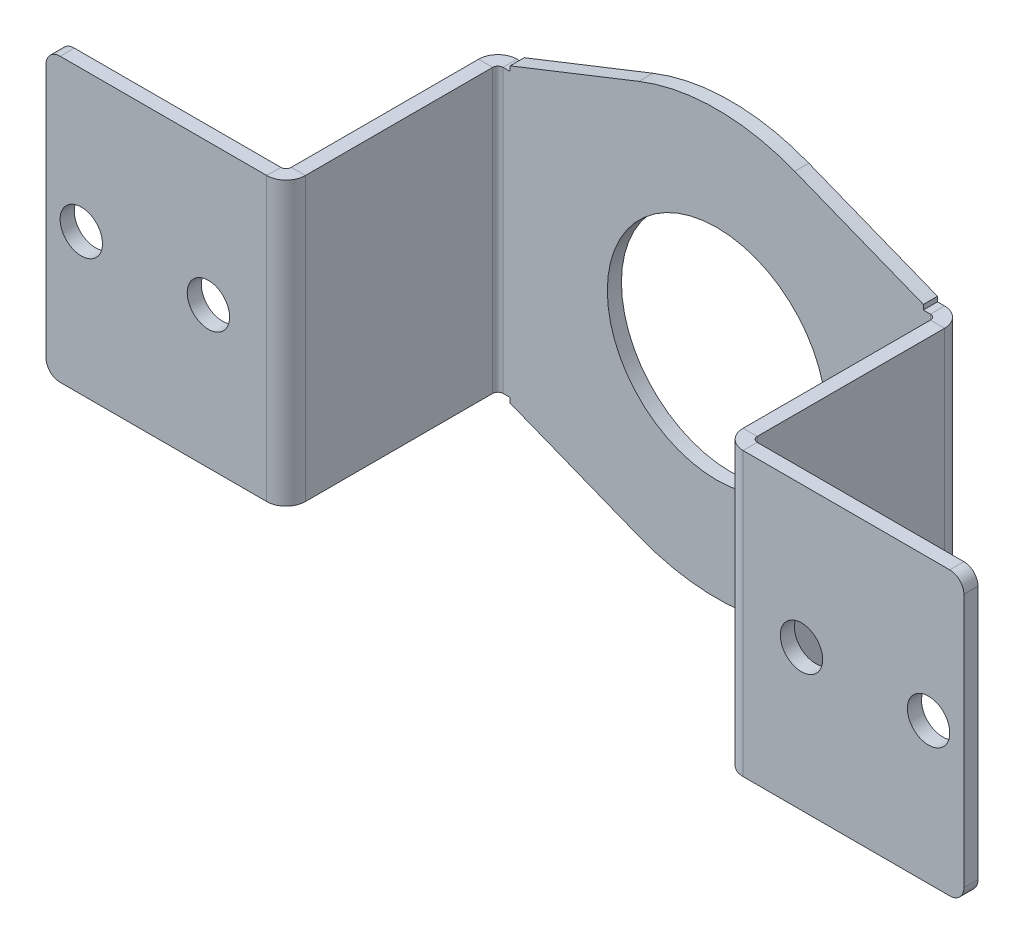
SolidWorks part; units mm, degrees
note: The reader was unsure of these and kept them because the rebuilt part matched: flange length of "Edge-Flange1", "Edge-Flange2".
material "1023 Carbon Steel Sheet (SS)"
ref_plane "Front Plane" through (0, 0, 0) normal (0, 0, 1) x (1, 0, 0)
ref_plane "Top Plane" through (0, 0, 0) normal (0, 1, 0) x (1, 0, 0)
ref_plane "Right Plane" through (0, 0, 0) normal (1, 0, 0) x (0, 0, -1)
sketch "Sketch1" plane through (0, 0, 0) normal (0, 0, 1) x (1, 0, 0)
  line L0 (0, 0) -> (-65, 0) construction
  line L2 (-31, 20) -> (-11.0341, 27.8971)
  line L3 (-31, -20) -> (-11.0341, -27.8971)
  line L4 (-31, 20) -> (-31, -20)
  line L5 (0, 0) -> (0, 30) construction
  line L6 (31, -20) -> (11.0341, -27.8971)
  line L7 (31, 20) -> (31, -20)
  line L8 (31, 20) -> (11.0341, 27.8971)
  circle A0 centre (0, 0) radius 15.5
  arc A1 (-11.0341, -27.8971) -> (11.0341, -27.8971) centre (0, 0) ccw
  arc A2 (11.0341, 27.8971) -> (-11.0341, 27.8971) centre (0, 0) ccw
  point P7 (-65, 0)
  point P13 (-31, 0)
  dimension "D1" = 31
  dimension "D2" = 60
  dimension "D3" = 40
  dimension "D5" = 31
base flange "Base-Flange1" sketch "Sketch1" thickness 2 reverse thickness direction no parameters "D1"=0.7366
edge flange "Edge-Flange1" sketch "Sketch8" flange profiles "Sketch8", "Sketch10" flange angle 90 flange length 30 flange position material outside bend radius 0.7366 thickness 2 relief rectangular parameters "D6"=10, "D8"=1
sketch "Sketch8" plane through (-31, 0, 0) normal (-1, 0, 0) x (0, -1, 0)
  line L2 (-20, 0) -> (-20, 28)
  line L3 (-20, 28) -> (20, 28)
  line L4 (20, 28) -> (20, 0)
  line L7 (-20, 0) -> (20, 0) construction
  line L8 (-20, 0) -> (20, 0)
sketch "Sketch10" plane through (31, 0, 0) normal (1, 0, 0) x (0, 1, 0)
  line L0 (-20, 0) -> (20, 0) construction
  line L1 (-20, 0) -> (20, 0)
  line L2 (-20, 0) -> (-20, 28)
  line L3 (-20, 28) -> (20, 28)
  line L4 (20, 28) -> (20, 0)
bend "EdgeBend1" bend radius 0.7366 bend angle 90 parameters "D5"=1
bend "EdgeBend2" bend radius 0.7366 bend angle 90 parameters "D5"=3
edge flange "Edge-Flange2" sketch "Sketch15" flange profiles "Sketch15", "Sketch16" flange angle 90 flange length 34 flange position material outside bend radius 0.7366 thickness 2 relief rectangular parameters "D6"=10, "D8"=1
sketch "Sketch15" plane through (-33, 0, 28) normal (0, 0, 1) x (0, 1, 0)
  line L2 (-20, 0) -> (-20, 32)
  line L3 (-20, 32) -> (20, 32)
  line L4 (20, 32) -> (20, 0)
  line L7 (-20, 0) -> (20, 0) construction
  line L8 (-20, 0) -> (20, 0)
sketch "Sketch16" plane through (33, 0, 28) normal (0, 0, 1) x (0, -1, 0)
  line L0 (-20, 0) -> (20, 0) construction
  line L1 (-20, 0) -> (20, 0)
  line L2 (-20, 0) -> (-20, 32)
  line L3 (-20, 32) -> (20, 32)
  line L4 (20, 32) -> (20, 0)
bend "EdgeBend3" bend radius 0.7366 bend angle 90 parameters "D5"=4
bend "EdgeBend4" bend radius 0.7366 bend angle 90 parameters "D5"=5
sketch "Sketch17" plane through (0, 0, 28) normal (0, 0, -1) x (-1, 0, 0)
  circle A1 centre (60, 0) radius 3
  circle A2 centre (42, 0) radius 3
  circle A3 centre (-60, 0) radius 3
  circle A4 centre (-42, 0) radius 3
  dimension "D1" = 6
  dimension "D2" = 6
  dimension "D3" = 42
  dimension "D4" = 60
  dimension "D5" = 42
  dimension "D6" = 60
extrude "Cut-Extrude1" cut sketch "Sketch17" against normal blind 10 normal cut yes
fillet "Fillet1" radius 2 4 edges at (-65, -20, 29) (65, 20, 29) (65, -20, 29) (-65, 20, 29)
sketch "Bend-Lines1" [suppressed] plane through (0, 0, 0) normal (0, 1, 0) x (1, 0, 0)
sketch "Bounding-Box1" [suppressed] plane through (0, 0, 0) normal (0, 1, 0) x (1, 0, 0)
sheet metal parameters "Sheet-Metal1" thickness 2 parameters "D1"=0.7366
flat pattern "Flat-Pattern1" [suppressed]
sketch "Bend-Lines2" plane through (0, 0, 0) normal (0, 1, 0) x (1, 0, 0)
sketch3d "Bounding-Box2" [suppressed]
  line L0 (30.9987, 30.0007, 0) -> (-31.0001, 29.9992, 0) construction
  line L1 (31.0001, -29.9992, 0) -> (-30.9987, -30.0007, 0) construction
  line L2 (30.9987, 30.0007, 0) -> (31.0001, -29.9992, 0) construction
  line L3 (-31.0001, 29.9992, 0) -> (-30.9987, -30.0007, 0) construction
sheet metal parameters "Sheet-Metal2" thickness 2 parameters "D1"=0.7366
flat pattern "Flat-Pattern1"
sketch "Bend-Lines2" plane through (0, 0, 0) normal (0, 0, 1) x (1, 0, 0)
  line L0 (-31.6273, 25.4296) -> (-31.6273, -25.4296) construction
  line L1 (-31.6273, 25.4296) -> (-31.6273, -25.4296) construction
  line L2 (31.6273, -25.4296) -> (31.6273, 25.4296) construction
  line L3 (31.6273, -25.4296) -> (31.6273, 25.4296) construction
sketch3d "Bounding-Box2" [suppressed]
  line L0 (-51.2533, 30.0012, 0) -> (51.2548, 29.9987, 0) construction
  line L1 (-51.2548, -29.9987, 0) -> (51.2533, -30.0012, 0) construction
  line L2 (-51.2533, 30.0012, 0) -> (-51.2548, -29.9987, 0) construction
  line L3 (51.2548, 29.9987, 0) -> (51.2533, -30.0012, 0) construction
bend of the flat pattern "Flatten-<EdgeBend1>1"
bend of the flat pattern "Flatten-<EdgeBend2>1"
sheet metal parameters "Sheet-Metal3" thickness 2 parameters "D1"=0.7366
flat pattern "Flat-Pattern1"
sketch "Bend-Lines2" plane through (0, 0, 0) normal (0, 0, 1) x (1, 0, 0)
  line L0 (-31.6273, 25.4296) -> (-31.6273, -25.4296) construction
  line L1 (-31.6273, 25.4296) -> (-31.6273, -25.4296) construction
  line L2 (31.6273, -25.4296) -> (31.6273, 25.4296) construction
  line L3 (31.6273, -25.4296) -> (31.6273, 25.4296) construction
  line L4 (51.882, -25.4296) -> (51.882, 25.4296) construction
  line L5 (-51.882, 25.4296) -> (-51.882, -25.4296) construction
  line L6 (51.882, -25.4296) -> (51.882, 25.4296) construction
  line L7 (-51.882, 25.4296) -> (-51.882, -25.4296) construction
sketch3d "Bounding-Box2" [suppressed]
  line L0 (-84.508, 30.002, 0) -> (84.5094, 29.998, 0) construction
  line L1 (-84.5094, -29.998, 0) -> (84.508, -30.002, 0) construction
  line L2 (-84.508, 30.002, 0) -> (-84.5094, -29.998, 0) construction
  line L3 (84.5094, 29.998, 0) -> (84.508, -30.002, 0) construction
bend of the flat pattern "Flatten-<EdgeBend1>1"
bend of the flat pattern "Flatten-<EdgeBend2>1"
bend of the flat pattern "Flatten-<EdgeBend3>1"
bend of the flat pattern "Flatten-<EdgeBend4>1"
sheet metal parameters "Sheet-Metal4" thickness 2 parameters "D1"=0.7366
flat pattern "Flat-Pattern1"
sketch "Bend-Lines2" plane through (0, 0, 0) normal (0, 0, 1) x (1, 0, 0)
  line L0 (-31.6273, 20) -> (-31.6273, -20) construction
  line L1 (-31.6273, 20) -> (-31.6273, -20) construction
  line L2 (31.6273, -20) -> (31.6273, 20) construction
  line L3 (31.6273, -20) -> (31.6273, 20) construction
  line L4 (60.882, -20) -> (60.882, 20) construction
  line L5 (-60.882, 20) -> (-60.882, -20) construction
  line L6 (60.882, -20) -> (60.882, 20) construction
  line L7 (-60.882, 20) -> (-60.882, -20) construction
sketch3d "Bounding-Box2" [suppressed]
  line L0 (-93.5093, -30, 0) -> (93.5093, -30, 0) construction
  line L1 (-93.5093, 30, 0) -> (93.5093, 30, 0) construction
  line L2 (-93.5093, -30, 0) -> (-93.5093, 30, 0) construction
  line L3 (93.5093, -30, 0) -> (93.5093, 30, 0) construction
bend of the flat pattern "Flatten-<EdgeBend1>1"
bend of the flat pattern "Flatten-<EdgeBend2>1"
bend of the flat pattern "Flatten-<EdgeBend3>1"
bend of the flat pattern "Flatten-<EdgeBend4>1"
